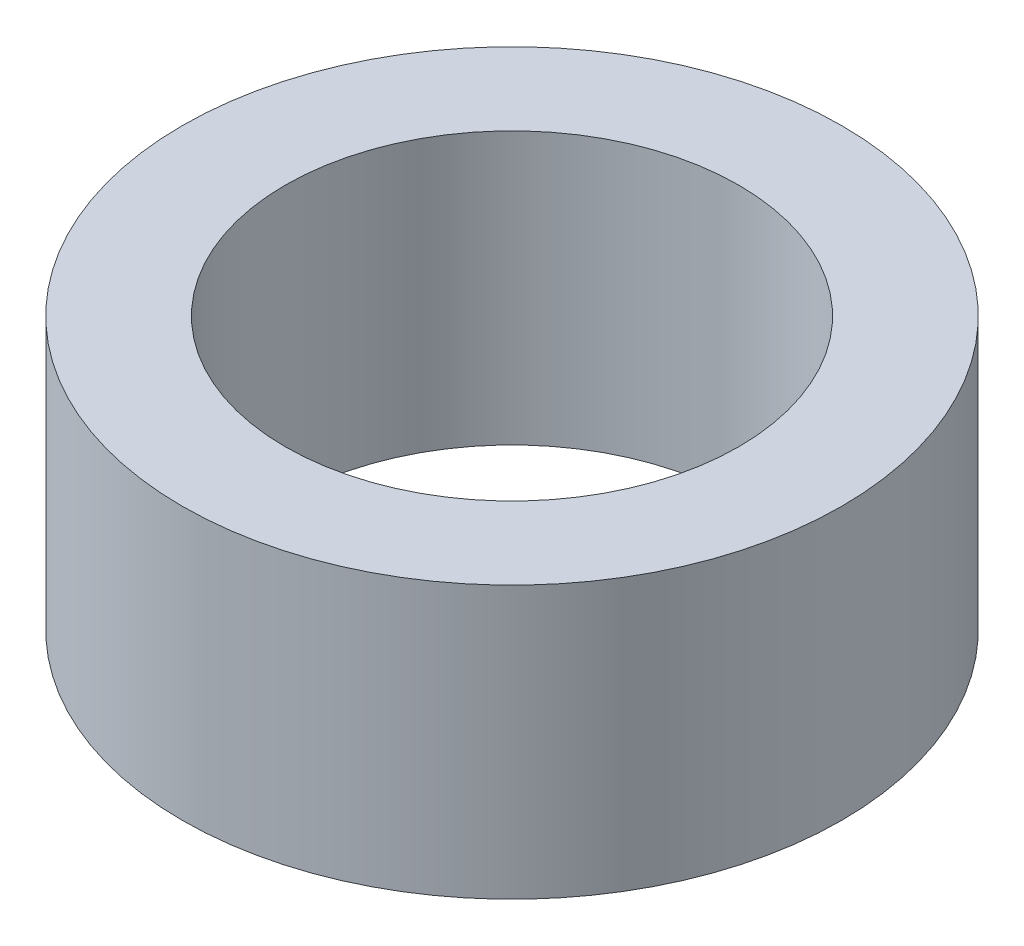
SolidWorks part; units mm, degrees
material "Alum Plate"
ref_plane "Front Plane" through (0, 0, 0) normal (0, 0, 1) x (1, 0, 0)
ref_plane "Top Plane" through (0, 0, 0) normal (0, 1, 0) x (1, 0, 0)
ref_plane "Right Plane" through (0, 0, 0) normal (1, 0, 0) x (0, 0, -1)
other "Bounding Box"
ref_plane "Default Plane" through (-8.9266, -12.7485, 0) normal (-0.1736, 0.9848, 0) x (0.9848, 0.1736, 0)
sketch "Sketch2" plane through (0, 0, 0) normal (0, 1, 0) x (1, 0, 0)
  circle A0 centre (0, 0) radius 7.9375
  circle A1 centre (0, 0) radius 11.5443
  dimension "D1" = 15.875
  dimension "D2" = 23.0886
extrude "Boss-Extrude1" add sketch "Sketch2" along normal mid plane 9.525
